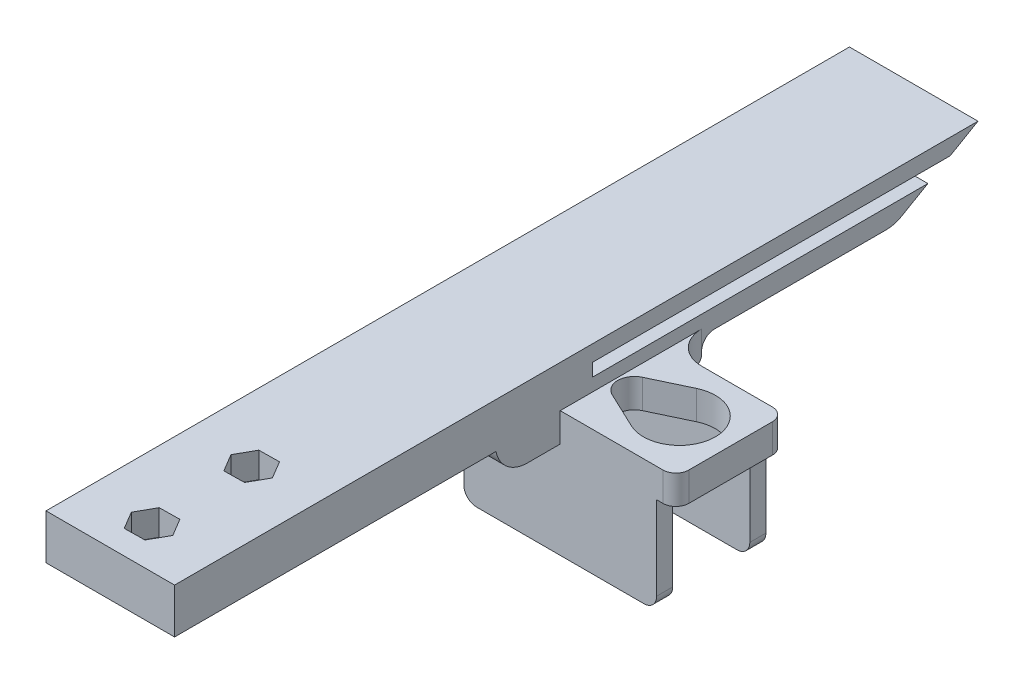
SolidWorks part; units mm, degrees
ref_plane "Front Plane" through (0, 0, 0) normal (0, 0, 1) x (1, 0, 0)
ref_plane "Top Plane" through (0, 0, 0) normal (0, 1, 0) x (1, 0, 0)
ref_plane "Right Plane" through (0, 0, 0) normal (1, 0, 0) x (0, 0, -1)
sketch "Sketch1" plane through (0, 0, 0) normal (0, 0, 1) x (1, 0, 0)
  line L1 (-26.5363, 10.2235) -> (-6.5363, 10.2235)
  line L2 (-26.5363, 10.2235) -> (-26.5363, 2.2235)
  line L3 (-26.5363, 2.2235) -> (-6.5363, 2.2235)
  line L4 (-6.5363, 10.2235) -> (-6.5363, 2.2235)
  dimension "D1" = 20
  dimension "D2" = 8
extrude "Boss-Extrude1" add sketch "Sketch1" against normal blind 125
sketch "Sketch2" plane through (0, 0, 0) normal (0, 0, 1) x (1, 0, 0)
  line L0 (-26.5363, 10.2235) -> (-26.5363, 2.2235) construction
  line L1 (-26.5363, 7.7235) -> (-22.1863, 7.7235)
  line L2 (-22.1863, 7.7235) -> (-22.1863, 5.7235)
  line L3 (-22.1863, 5.7235) -> (-23.6863, 5.7235)
  line L4 (-23.6863, 5.7235) -> (-23.6863, 4.2235)
  line L5 (-23.6863, 4.2235) -> (-22.1863, 4.2235)
  line L6 (-22.1863, 4.2235) -> (-22.1863, 2.7235)
  line L7 (-22.1863, 2.7235) -> (-20.5363, 2.7235)
  line L8 (-20.5363, 2.7235) -> (-20.5363, 7.7235)
  line L9 (-20.5363, 7.7235) -> (-12.5363, 7.7235)
  line L10 (-16.5363, 10.2235) -> (-16.5363, 5.2831) construction
  line L11 (-6.5363, 10.2235) -> (-26.5363, 10.2235) construction
  line L13 (-26.5363, 7.7235) -> (-26.5363, 2.2235)
  line L15 (-12.5363, 2.7235) -> (-12.5363, 7.7235)
  line L16 (-10.8863, 2.7235) -> (-12.5363, 2.7235)
  line L17 (-10.8863, 4.2235) -> (-10.8863, 2.7235)
  line L18 (-9.3863, 4.2235) -> (-10.8863, 4.2235)
  line L19 (-9.3863, 5.7235) -> (-9.3863, 4.2235)
  line L20 (-10.8863, 5.7235) -> (-9.3863, 5.7235)
  line L21 (-10.8863, 7.7235) -> (-10.8863, 5.7235)
  line L22 (-6.5363, 7.7235) -> (-10.8863, 7.7235)
  line L23 (-6.5363, 7.7235) -> (-6.5363, 2.2235)
  line L24 (-26.5363, 2.2235) -> (-6.5363, 2.2235)
  point P23 (-16.5363, 7.7235)
  dimension "D2" = 2.5
  dimension "D3" = 4.35
  dimension "D4" = 2
  dimension "D5" = 1.5
  dimension "D6" = 1.5
  dimension "D7" = 1.5
  dimension "D8" = 1.65
extrude "Cut-Extrude1" cut sketch "Sketch2" against normal blind 60
sketch "Sketch3" plane through (0, 10.2235, 0) normal (0, 1, 0) x (1, 0, 0)
  line L4 (-26.5363, 0) -> (-6.5363, 0)
  line L5 (-6.5363, 0) -> (-6.5363, 125)
  line L6 (-6.5363, 125) -> (-26.5363, 125)
  line L7 (-26.5363, 125) -> (-26.5363, 0)
  line L8 (-26.5363, 0) -> (-6.5363, 0)
  line L9 (-6.5363, 0) -> (-6.5363, 125)
  line L10 (-6.5363, 125) -> (-26.5363, 125)
  line L11 (-26.5363, 125) -> (-26.5363, 0)
  dimension "D1" = 0
extrude "Boss-Extrude2" add sketch "Sketch3" along normal blind 3
sketch "Sketch5" plane through (0, 0, -125) normal (0, 0, -1) x (-1, 0, 0)
  line L0 (6.5363, 10.7235) -> (11.0363, 10.7235)
  line L1 (6.5363, 2.2235) -> (6.5363, 13.2235) construction
  line L2 (11.0363, 10.7235) -> (11.0363, 8.7235)
  line L3 (11.0363, 8.7235) -> (6.5363, 8.7235)
  line L4 (6.5363, 8.7235) -> (6.5363, 10.7235)
  line L5 (6.5363, 13.2235) -> (26.5363, 13.2235) construction
  line L6 (16.5363, 13.2235) -> (16.5363, 8.5004) construction
  line L7 (22.0363, 8.7235) -> (26.5363, 8.7235)
  line L8 (22.0363, 10.7235) -> (22.0363, 8.7235)
  line L9 (26.5363, 10.7235) -> (22.0363, 10.7235)
  line L10 (26.5363, 8.7235) -> (26.5363, 10.7235)
  dimension "D1" = 4.5
  dimension "D2" = 2
  dimension "D3" = 2.5
extrude "Cut-Extrude2" cut sketch "Sketch5" against normal blind 60
sketch "Sketch9" plane through (-6.5363, 0, 0) normal (1, 0, 0) x (0, 0, -1)
  line L0 (60, 2.2235) -> (60, -12.7765)
  line L2 (77, -12.7765) -> (77, 2.2235)
  line L3 (125, 2.2235) -> (60, 2.2235) construction
  line L4 (77, 2.2235) -> (74.5, 2.2235)
  line L5 (74.5, 2.2235) -> (74.5, -12.7765)
  line L7 (62.5, -12.7765) -> (62.5, 2.2235)
  line L8 (62.5, 2.2235) -> (60, 2.2235)
  line L9 (60, -12.7765) -> (62.5, -12.7765)
  line L10 (74.5, -12.7765) -> (77, -12.7765)
  dimension "D1" = 2.5
  dimension "D2" = 15
  dimension "D3" = 12
extrude "Boss-Extrude5" add sketch "Sketch9" against normal blind 15 and the other way blind 15
sketch "Sketch10" plane through (-6.5363, 0, 0) normal (1, 0, 0) x (0, 0, -1)
  line L0 (60, 2.2235) -> (60, 7.7235) construction
  line L1 (77, 2.2235) -> (60, 2.2235)
  line L2 (77, 2.2235) -> (77, 6.7235)
  line L3 (77, 6.7235) -> (60, 6.7235)
  line L4 (60, 2.2235) -> (60, 6.7235)
  dimension "D1" = 4.5
extrude "Boss-Extrude6" add sketch "Sketch10" along normal blind 18
sketch "Sketch11" plane through (0, 2.2235, 0) normal (0, -1, 0) x (1, 0, 0)
  line L0 (11.4637, -60) -> (11.4637, -77) construction
  line L1 (-4.6506, -66.1939) -> (1.0637, -63.4834)
  line L2 (-4.6506, -70.8921) -> (1.0637, -73.6027)
  arc A0 (1.0637, -73.6027) -> (1.0637, -63.4834) centre (3.4637, -68.543) ccw
  arc A1 (-4.6506, -66.1939) -> (-4.6506, -70.8921) centre (-3.5363, -68.543) ccw
  dimension "D1" = 11.2
  dimension "D2" = 8
  dimension "D3" = 5.2
  dimension "D4" = 7
extrude "Cut-Extrude3" cut sketch "Sketch11" against normal through all
sketch "Sketch12" plane through (0, 2.2235, 0) normal (0, -1, 0) x (1, 0, 0)
  line L0 (8.4637, -62.5) -> (-21.5363, -62.5) construction
  line L1 (-14.7173, -69.7068) -> (-14.6567, -67.3982)
  line L2 (-14.6567, -67.3982) -> (-16.6257, -66.1914)
  line L3 (-16.6257, -66.1914) -> (-18.6553, -67.2932)
  line L4 (-18.6553, -67.2932) -> (-18.7159, -69.6018)
  line L5 (-18.7159, -69.6018) -> (-16.7469, -70.8086)
  line L6 (-16.7469, -70.8086) -> (-14.7173, -69.7068)
  line L7 (-21.5363, -60) -> (-21.5363, -62.5) construction
  circle A0 centre (-16.6863, -68.5) radius 2 construction
  dimension "D1" = 6
  dimension "D2" = 4.85
  dimension "D3" = 4
extrude "Cut-Extrude4" cut sketch "Sketch12" against normal blind 4
fillet "Fillet1" radius 5 1 edges at (-6.5363, 4.4735, -77)
fillet "Fillet2" radius 3 1 edges at (-11.5363, 2.2235, -77)
fillet "Fillet3" radius 5 2 edges at (-21.5363, 2.2235, -61.25) (-21.5363, 2.2235, -77.25)
fillet "Fillet4" radius 2 2 edges at (11.4637, 4.4735, -77) (11.4637, 4.4735, -60)
ref_plane "Plane1" through (0, -44.209, -25.5241) normal (0, 0.866, 0.5) x (-1, 0, 0)
sketch "Sketch13" plane through (0, -44.209, -25.5241) normal (0, 0.866, 0.5) x (-1, 0, 0)
  line L5 (39.5856, -85.4228) -> (-7.1505, -85.4228)
  line L6 (39.5856, -85.4228) -> (39.5856, -132.2421)
  line L7 (39.5856, -132.2421) -> (-7.1505, -132.2421)
  line L8 (-7.1505, -85.4228) -> (-7.1505, -132.2421)
extrude "Cut-Extrude5" cut sketch "Sketch13" against normal blind 30
sketch "Sketch14" plane through (0, 2.2235, 0) normal (0, -1, 0) x (1, 0, 0)
  line L4 (-6.5363, -82) -> (-37.0735, -82)
  line L5 (-6.5363, -82) -> (-6.5363, -132.6125)
  line L6 (-6.5363, -132.6125) -> (-37.0735, -132.6125)
  line L7 (-37.0735, -82) -> (-37.0735, -132.6125)
extrude "Cut-Extrude6" cut sketch "Sketch14" against normal blind 3.5
fillet "Fillet5" radius 5 1 edges at (-16.5363, 5.7235, -112.0096) type face fillet first side face at (-16.5363, 5.7235, -97.0048) second side face at (-16.5363, 9.6401, -118.7935)
fillet "Fillet6" radius 2 1 edges at (-16.5363, 5.7235, -82) type face fillet first side face at (-16.5363, 3.9735, -82) second side face at (-16.5363, 5.7235, -96.3349)
fillet "Fillet7" radius 1 1 edges at (-16.5363, 2.2235, -82) type face fillet first side face at (-16.4578, 2.2235, -80.9946) second side face at (-16.5363, 2.9735, -82)
fillet "Fillet8" radius 2 4 edges at (8.4637, -12.7765, -61.25) (8.4637, -12.7765, -75.75) (-21.5363, -12.7765, -61.25) (-21.5363, -12.7765, -75.75)
sketch "Sketch15" plane through (0, 2.7235, 0) normal (0, -1, 0) x (1, 0, 0)
  line L1 (-26.5363, 0) -> (-6.5363, 0)
  line L2 (-26.5363, 0) -> (-26.5363, -60)
  line L3 (-26.5363, -60) -> (-6.5363, -60)
  line L4 (-6.5363, 0) -> (-6.5363, -60)
extrude "Cut-Extrude7" cut sketch "Sketch15" against normal up to surface (5 mm away) up to face at (-16.5363, 7.7235, -30)
sketch "Sketch16" plane through (0, 7.7235, 0) normal (0, -1, 0) x (1, 0, 0)
  line L4 (-6.5363, 0) -> (-26.5363, 0)
  line L5 (-26.5363, 0) -> (-26.5363, -60)
  line L6 (-26.5363, -60) -> (-6.5363, -60)
  line L7 (-6.5363, -60) -> (-6.5363, 0)
  line L8 (-6.5363, 0) -> (-26.5363, 0)
  line L9 (-26.5363, 0) -> (-26.5363, -60)
  line L10 (-26.5363, -60) -> (-6.5363, -60)
  line L11 (-6.5363, -60) -> (-6.5363, 0)
  dimension "D1" = 0
extrude "Boss-Extrude7" add sketch "Sketch16" along normal blind 1.5
sketch "Sketch17" plane through (0, 6.2235, 0) normal (0, -1, 0) x (1, 0, 0)
  line L0 (-6.5363, -60) -> (-6.5363, 0) construction
  line L1 (-26.5363, -60) -> (-6.5363, -60)
  line L2 (-26.5363, -60) -> (-26.5363, -50)
  line L3 (-26.5363, -50) -> (-6.5363, -50)
  line L4 (-6.5363, -60) -> (-6.5363, -50)
  dimension "D1" = 10
extrude "Boss-Extrude8" add sketch "Sketch17" along normal up to surface (4 mm away) up to face at (-16.4133, 2.2235, -80.4979)
fillet "Fillet9" radius 5 1 edges at (-16.5363, 2.2235, -50)
sketch "Sketch18" plane through (0, 13.2235, 0) normal (0, 1, 0) x (1, 0, 0)
  line L0 (-26.5363, 0) -> (-6.5363, 0) construction
  line L1 (-6.5363, 0) -> (-6.5363, 125) construction
  circle A0 centre (-16.5363, 22) radius 1.75
  circle A1 centre (-16.5363, 6.5) radius 1.75
  dimension "D1" = 3.5
  dimension "D2" = 15.5
  dimension "D4" = 10
  dimension "D3" = 6.5
extrude "Cut-Extrude8" cut sketch "Sketch18" against normal through all
sketch "Sketch19" plane through (0, 13.2235, 0) normal (0, 1, 0) x (1, 0, 0)
  line L1 (-18.0877, 19.2241) -> (-14.908, 19.2685)
  line L2 (-14.908, 19.2685) -> (-13.3566, 22.0444)
  line L3 (-13.3566, 22.0444) -> (-14.9849, 24.7759)
  line L4 (-14.9849, 24.7759) -> (-18.1646, 24.7315)
  line L5 (-18.1646, 24.7315) -> (-19.716, 21.9556)
  line L6 (-19.716, 21.9556) -> (-18.0877, 19.2241)
  line L7 (-14.908, 3.7685) -> (-13.3566, 6.5444)
  line L8 (-13.3566, 6.5444) -> (-14.9849, 9.2759)
  line L9 (-14.9849, 9.2759) -> (-18.1646, 9.2315)
  line L10 (-18.1646, 9.2315) -> (-19.716, 6.4556)
  line L11 (-19.716, 6.4556) -> (-18.0877, 3.7241)
  line L12 (-18.0877, 3.7241) -> (-14.908, 3.7685)
  circle A0 centre (-16.5363, 22) radius 2.754 construction
  circle A1 centre (-16.5363, 6.5) radius 2.754 construction
  circle A2 centre (-16.5363, 6.5) radius 1.75 construction
  circle A3 centre (-16.5363, 22) radius 1.75 construction
  dimension "D1" = 3.18
extrude "Cut-Extrude9" cut sketch "Sketch19" against normal blind 4
